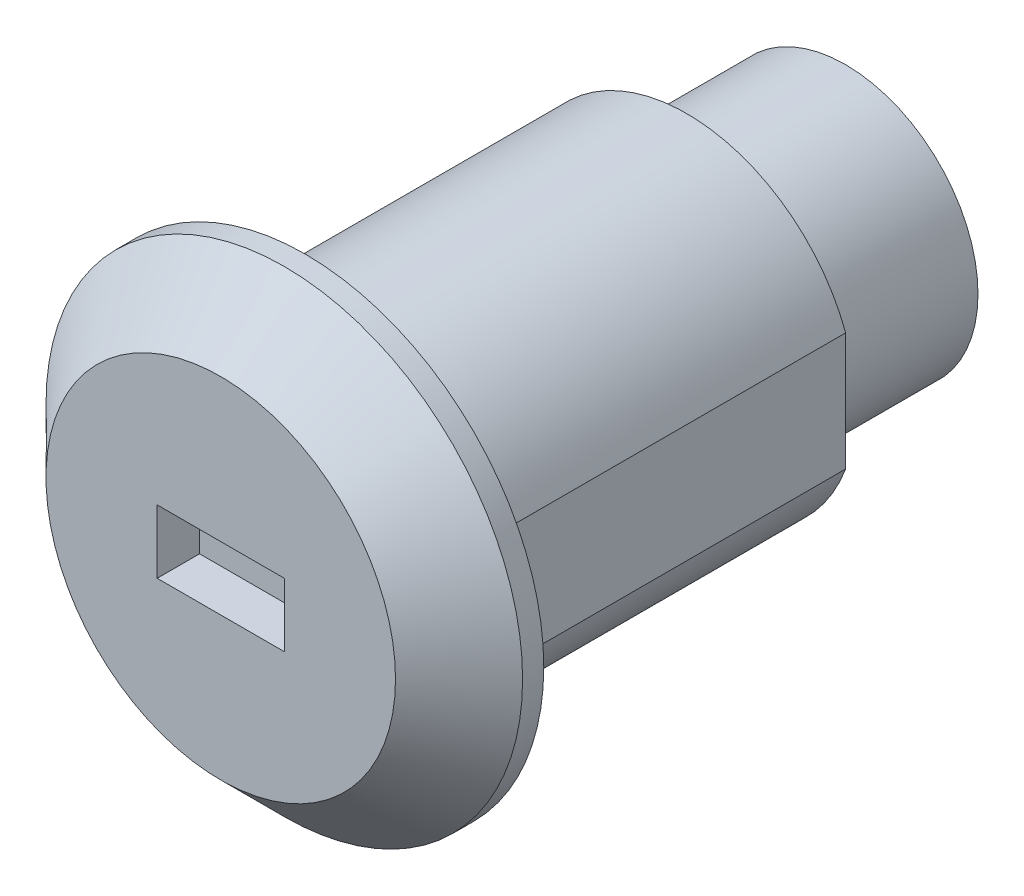
SolidWorks part; units mm, degrees
ref_plane "前视基准面" through (0, 0, 0) normal (0, 0, 1) x (1, 0, 0)
ref_plane "上视基准面" through (0, 0, 0) normal (0, 1, 0) x (1, 0, 0)
ref_plane "右视基准面" through (0, 0, 0) normal (1, 0, 0) x (0, 0, -1)
sketch "草图1" plane through (0, 0, 0) normal (0, 0, 1) x (1, 0, 0)
  line L0 (0, 0) -> (0, 36.6059) construction
  line L1 (0, 36.6059) -> (0, -30.2559) construction
  line L2 (-35.8588, 0) -> (29.1353, 0) construction
  circle A0 centre (0, 0) radius 11.25
  dimension "D1" = 22.5
extrude "拉伸1" add sketch "草图1" along normal blind 4
chamfer "倒角1" distance 3 angle 45 1 edges at (11.25, 0, 4)
sketch "草图2" plane through (0, 0, 4) normal (0, 0, 1) x (1, 0, 0)
  line L0 (-6.6609, 0) -> (5.0173, 0) construction
  line L1 (0, 5.7093) -> (0, -4.7145) construction
  line L3 (-3, 1.5) -> (3, 1.5)
  line L4 (-3, 1.5) -> (-3, -1.5)
  line L5 (-3, -1.5) -> (3, -1.5)
  line L6 (3, 1.5) -> (3, -1.5)
  dimension "D1" = 6
  dimension "D2" = 3
extrude "切除-拉伸1" cut sketch "草图2" against normal blind 2
sketch "草图3" plane through (0, 0, 0) normal (0, 0, -1) x (-1, 0, 0)
  line L0 (0, 13.2042) -> (0, -14.0761) construction
  line L1 (-13.3287, 0) -> (13.6401, 0) construction
  line L2 (-7.5, 2.7839) -> (-7.5, -2.7839)
  line L3 (7.5, 2.7839) -> (7.5, -2.7839)
  arc A0 (-7.5, -2.7839) -> (7.5, -2.7839) centre (0, 0) ccw
  arc A1 (7.5, 2.7839) -> (-7.5, 2.7839) centre (0, 0) ccw
  dimension "D1" = 16
  dimension "D2" = 15
extrude "拉伸2" add sketch "草图3" along normal offset from surface (18 mm away) 22 up to face at (0, 0, 4)
sketch "草图4" plane through (0, 0, -18) normal (0, 0, -1) x (-1, 0, 0)
  circle A0 centre (0, 0) radius 6.25
  dimension "D1" = 12.5
extrude "拉伸3" add sketch "草图4" along normal offset from surface (7.5 mm away) 29.5 up to face at (0, 0, 4)
